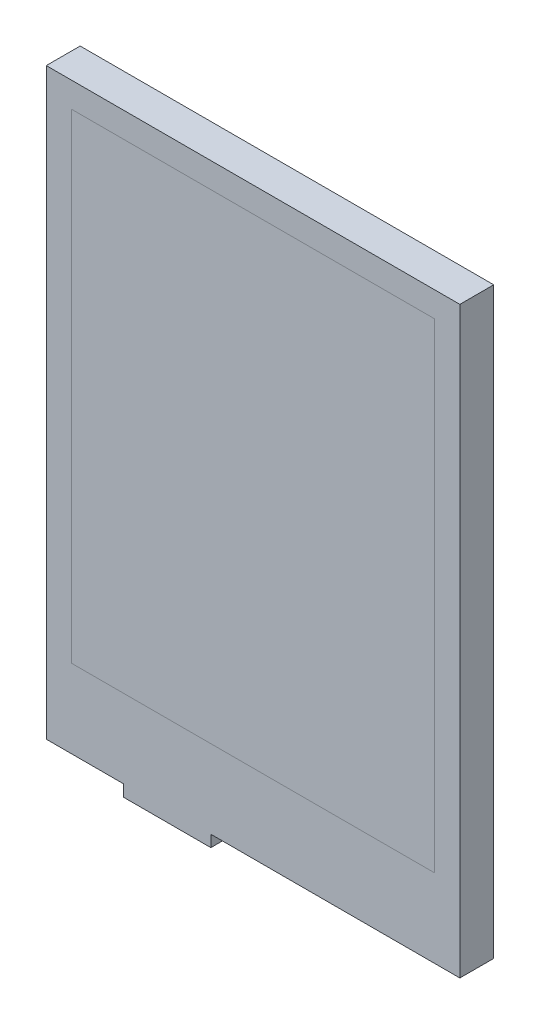
SolidWorks part; units mm, degrees
ref_plane "Front Plane" through (0, 0, 0) normal (0, 0, 1) x (1, 0, 0)
ref_plane "Top Plane" through (0, 0, 0) normal (0, 1, 0) x (1, 0, 0)
ref_plane "Right Plane" through (0, 0, 0) normal (1, 0, 0) x (0, 0, -1)
sketch "main_features_sketch" plane through (0, 0, 0) normal (0, 0, 1) x (1, 0, 0)
  line L0 (-13.1, 0.02) -> (-17, 0.02)
  line L1 (18.76, 24.78) -> (-18.76, 24.78)
  line L2 (18.76, 24.78) -> (18.76, -24.78)
  line L3 (18.76, -24.78) -> (-18.76, -24.78)
  line L4 (-18.76, 24.78) -> (-18.76, -24.78)
  line L5 (0, -24.78) -> (0, 24.78) construction
  line L6 (18.76, 0) -> (-18.76, 0) construction
  line L7 (21.36, 27.38) -> (-21.36, 27.38)
  line L8 (21.36, 27.38) -> (21.36, -32.88)
  line L9 (21.36, -32.88) -> (-21.36, -32.88)
  line L10 (-21.36, 27.38) -> (-21.36, -32.88)
  line L11 (0, -32.88) -> (0, 27.38) construction
  line L12 (21.36, -2.75) -> (-21.36, -2.75) construction
  line L13 (-4.36, -34.08) -> (-13.36, -34.08)
  line L14 (-4.36, -34.08) -> (-4.36, -32.88)
  line L15 (-4.36, -32.88) -> (-13.36, -32.88)
  line L16 (-13.36, -34.08) -> (-13.36, -32.88)
  line L17 (-17, 0.02) -> (-17, -9.48)
  line L18 (-17, -9.48) -> (-13.1, -9.48)
  line L19 (-13.1, 0.02) -> (-13.1, -9.48)
  point P0 (0, 0)
  point P4 (0, 0)
  point P17 (-8.86, -34.08)
  dimension "D1" = 49.56
  dimension "D2" = 37.52
  dimension "D3" = 42.72
  dimension "D4" = 2.6
  dimension "D5" = 2.6
  dimension "D6" = 60.26
  dimension "D7" = 1.2
  dimension "D8" = 9
  dimension "D9" = 12.5
  dimension "D10" = 9.5
  dimension "D11" = 3.9
  dimension "D12" = 32.9
  dimension "D13" = 4.36
extrude "Boss-Extrude1" add sketch "main_features_sketch" along normal blind 3.5 contours L7 L10 L9 L8 L4 L1 L2 L3 | L16 L13 L14 L9 region at (20.6213, -2.75, 0) region at (-8.86, -33.48, 0)
extrude "Boss-Extrude2" add sketch "Sketch1<3>" along normal up to vertex (3.5 mm away) separate body contours L1 L4 L3 L2 | L19 L0 L17 L18 region at (-15.05, -4.73, 0) region at (0.306, 0.0962, 0) up to point (-21.36, 27.38, 3.5)
sketch "Sketch1<3>" plane through (0, 0, 0) normal (0, 0, 1) x (1, 0, 0) same geometry as "main_features_sketch"
extrude "Cut-Extrude1" cut sketch "main_features_sketch<4>" along normal blind 0.3 contours L19 L0 L17 L18 region at (-15.05, -4.73, 0)
sketch "main_features_sketch<4>" plane through (0, 0, 0) normal (0, 0, 1) x (1, 0, 0) same geometry as "main_features_sketch"
extrude "Boss-Extrude3" add sketch "main_features_sketch<5>" along normal blind 0.3 separate body contours L19 L0 L17 L18 region at (-15.05, -4.73, 0)
sketch "main_features_sketch<5>" plane through (0, 0, 0) normal (0, 0, 1) x (1, 0, 0) same geometry as "main_features_sketch"
